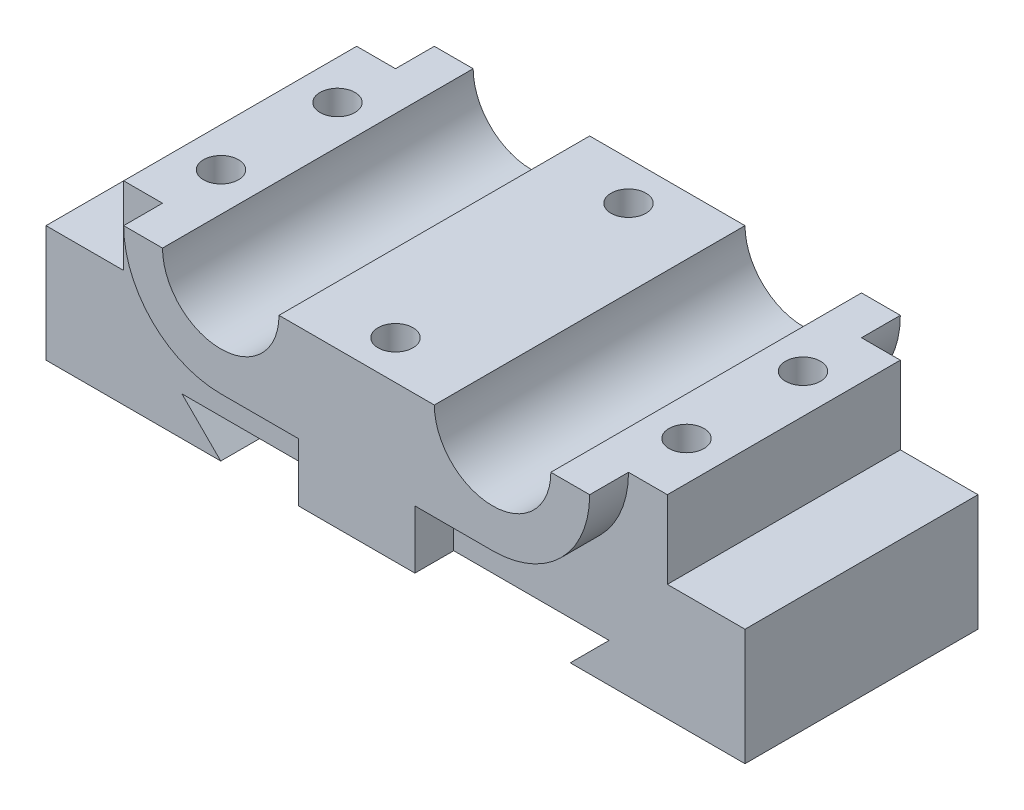
SolidWorks part; units mm, degrees
ref_plane "Front Plane" through (0, 0, 0) normal (0, 0, 1) x (1, 0, 0)
ref_plane "Top Plane" through (0, 0, 0) normal (0, 1, 0) x (1, 0, 0)
ref_plane "Right Plane" through (0, 0, 0) normal (1, 0, 0) x (0, 0, -1)
sketch "Sketch1" plane through (0, 0, 0) normal (0, 0, 1) x (1, 0, 0)
  line L1 (10, 9.3349) -> (-10, 9.3349)
  line L2 (-25, 9.3349) -> (-35, 9.3349)
  line L3 (-35, 9.3349) -> (-35, -0.6651)
  line L4 (-35, -0.6651) -> (-45, -0.6651)
  line L5 (-45, -0.6651) -> (-45, -15.6651)
  line L6 (-45, -15.6651) -> (-22.5, -15.6651)
  line L7 (-22.5, -15.6651) -> (-27.5, -10.6651)
  line L8 (-27.5, -10.6651) -> (27.5, -10.6651)
  line L10 (22.5, -15.6651) -> (27.5, -10.6651)
  line L11 (45, -15.6651) -> (22.5, -15.6651)
  line L12 (45, -0.6651) -> (45, -15.6651)
  line L13 (35, -0.6651) -> (45, -0.6651)
  line L14 (35, 9.3349) -> (35, -0.6651)
  line L15 (25, 9.3349) -> (35, 9.3349)
  arc A0 (-25, 9.3349) -> (-10, 9.3349) centre (-17.5, 9.3349) ccw
  arc A1 (25, 9.3349) -> (10, 9.3349) centre (17.5, 9.3349) cw
  dimension "D4" = 7.5
  dimension "D3" = 10
  dimension "D5" = 15
  dimension "D7" = 45
  dimension "D9" = 5
extrude "Boss-Extrude1" add sketch "Sketch1" along normal blind 15 and the other way blind 15
sketch "Sketch2" plane through (0, 0, 15) normal (0, 0, 1) x (1, 0, 0)
  line L0 (-25, 9.3349) -> (-30, 9.3349)
  line L1 (-25, 9.3349) -> (-35, 9.3349) construction
  line L2 (-17.5, -3.1651) -> (-7.5, -3.1651)
  line L3 (-7.5, -3.1651) -> (-7.5, -10.6651)
  line L4 (-27.5, -10.6651) -> (27.5, -10.6651) construction
  line L5 (-7.5, -10.6651) -> (7.5, -10.6651)
  line L6 (-10, 9.3349) -> (10, 9.3349)
  line L9 (7.5, -3.1651) -> (7.5, -10.6651)
  line L10 (17.5, -3.1651) -> (7.5, -3.1651)
  line L11 (25, 9.3349) -> (30, 9.3349)
  arc A0 (-10, 9.3349) -> (-25, 9.3349) centre (-17.5, 9.3349) cw
  arc A1 (-25, 9.3349) -> (-10, 9.3349) centre (-17.5, 9.3349) ccw construction
  arc A2 (-30, 9.3349) -> (-17.5, -3.1651) centre (-17.5, 9.3349) ccw
  arc A3 (30, 9.3349) -> (17.5, -3.1651) centre (17.5, 9.3349) cw
  arc A4 (10, 9.3349) -> (25, 9.3349) centre (17.5, 9.3349) ccw
  dimension "D1" = 12.5
extrude "Boss-Extrude2" add sketch "Sketch2" along normal blind 5
sketch "Sketch4" plane through (0, 0, -15) normal (0, 0, -1) x (-1, 0, 0)
  line L0 (-35, 9.3349) -> (-25, 9.3349) construction
  line L1 (-10, 9.3349) -> (10, 9.3349)
  line L3 (-30, 9.3349) -> (-25, 9.3349)
  line L4 (-17.5, -3.1651) -> (-7.4679, -3.1651)
  line L6 (-7.4679, -3.1651) -> (-7.5, -10.6651)
  line L8 (-7.5, -10.6651) -> (7.5, -10.6651)
  line L9 (7.4679, -3.1651) -> (7.5, -10.6651)
  line L10 (17.5, -3.1651) -> (7.4679, -3.1651)
  line L11 (30, 9.3349) -> (25, 9.3349)
  arc A0 (-10, 9.3349) -> (-25, 9.3349) centre (-17.5, 9.3349) cw
  arc A1 (-30, 9.3349) -> (-17.5, -3.1651) centre (-17.5, 9.3349) ccw
  arc A2 (30, 9.3349) -> (17.5, -3.1651) centre (17.5, 9.3349) cw
  arc A3 (10, 9.3349) -> (25, 9.3349) centre (17.5, 9.3349) ccw
  dimension "D1" = 12.5
extrude "Boss-Extrude3" add sketch "Sketch4" along normal blind 5
sketch "Sketch5" plane through (0, 9.3349, 0) normal (0, 1, 0) x (1, 0, 0)
  line L0 (-30, -15) -> (-35, -15) construction
  line L1 (0, 0) -> (0, 27.1075) construction
  line L2 (0, 0) -> (18.8153, 0) construction
  circle A0 centre (0, -15) radius 2.25
  circle A1 centre (-29.9686, -7.5) radius 2.25
  circle A2 centre (29.9686, -7.5) radius 2.25
  circle A3 centre (29.9686, 7.5) radius 2.25
  circle A4 centre (-29.9686, 7.5) radius 2.25
  circle A5 centre (0, 15) radius 2.25
  dimension "D1" = 4.5
  dimension "D2" = 4.5
  dimension "D3" = 7.5
  dimension "D4" = 15
extrude "Cut-Extrude1" cut sketch "Sketch5" against normal blind 15
